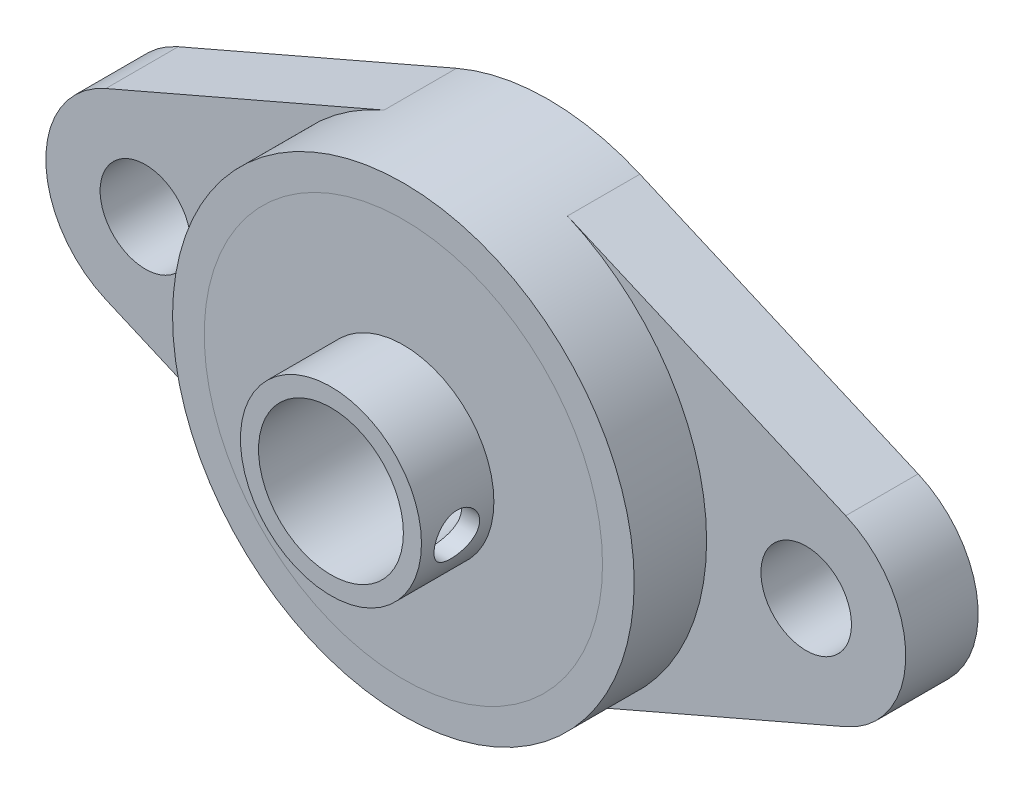
SolidWorks part; units mm, degrees
material "acero"
ref_plane "Alzado" through (0, 0, 0) normal (0, 0, 1) x (1, 0, 0)
ref_plane "Planta" through (0, 0, 0) normal (0, 1, 0) x (1, 0, 0)
ref_plane "Vista lateral" through (0, 0, 0) normal (1, 0, 0) x (0, 0, -1)
sketch "Croquis1" plane through (0, 0, 0) normal (0, 0, 1) x (1, 0, 0)
  line L0 (-18.25, 0) -> (0, 0) construction
  line L1 (0, 0) -> (18.25, 0) construction
  line L2 (-20.4349, -5.0474) -> (-5.0651, -11.7008)
  line L3 (5.0651, -11.7008) -> (20.4349, -5.0474)
  line L4 (5.0651, 11.7008) -> (20.4349, 5.0474)
  line L5 (-20.4349, 5.0474) -> (-5.0651, 11.7008)
  arc A0 (-5.0651, -11.7008) -> (5.0651, -11.7008) centre (0, 0) ccw
  circle A1 centre (0, 0) radius 5
  arc A2 (20.4349, -5.0474) -> (20.4349, 5.0474) centre (18.25, 0) ccw
  circle A3 centre (-18.25, 0) radius 2.5
  circle A4 centre (18.25, 0) radius 2.5
  arc A5 (-20.4349, 5.0474) -> (-20.4349, -5.0474) centre (-18.25, 0) ccw
  arc A7 (5.0651, 11.7008) -> (-5.0651, 11.7008) centre (0, 0) ccw
  dimension "D2" = 5.5
  dimension "D3" = 25.5
  dimension "D4" = 5
  dimension "D5" = 10
  dimension "D1" = 36.5
extrude "Saliente-Extruir1" add sketch "Croquis1" along normal blind 4
sketch "Croquis2" plane through (0, 0, 4) normal (0, 0, 1) x (1, 0, 0)
  circle A0 centre (0, 0) radius 11
  circle A1 centre (0, 0) radius 12.75
  arc A2 (-5.0651, -11.7008) -> (5.0651, -11.7008) centre (0, 0) ccw construction
  dimension "D1" = 22
extrude "Saliente-Extruir2" add sketch "Croquis2" along normal blind 4
sketch "Croquis3" plane through (0, 0, 4) normal (0, 0, 1) x (1, 0, 0)
  circle A0 centre (0, 0) radius 5
  circle A1 centre (0, 0) radius 11
  circle A2 centre (0, 0) radius 11
  dimension "D2" = 10
  dimension "D1" = 0
extrude "Saliente-Extruir3" add sketch "Croquis3" along normal blind 4 separate body
sketch "Croquis5" plane through (0, 0, 0) normal (0, 0, 1) x (1, 0, 0)
  circle A0 centre (0, 0) radius 5
  circle A1 centre (0, 0) radius 4
  dimension "D1" = 8
  dimension "D2" = 10
extrude "Saliente-Extruir4" add sketch "Croquis5" along normal blind 12 separate body
combine bodies "Combinar1" operation type add bodies to combine 106 107
ref_plane "Plane1" through (5, 0, 0) normal (1, 0, 0) x (0, 0, -1)
hole_wizard "M3 Tapped Hole1" positions "Sketch3" profile "Sketch2" tap size "M3" standard "DIN"
sketch "Sketch3" plane through (5, 0, 0) normal (1, 0, 0) x (0, 0, -1)
  line L0 (-12, 5) -> (-12, -5) construction
  point P0 (-10, -0.6713)
  dimension "D1" = 2
sketch "Sketch2" plane through (5, -0.6713, 10) normal (0, 1, 0) x (0, 0, -1)
  line L0 (0, 0) -> (0, 6.2511)
  line L1 (0, 6.2511) -> (1.25, 5.5)
  line L2 (1.25, 5.5) -> (1.25, 0)
  line L5 (1.25, 0) -> (0, 0)
  line L10 (0, 6.2511) -> (-1.25, 5.5) construction
  line L11 (0, -6.35) -> (0, 107.95) construction
  dimension "Tap Drill Dia." = 2.5
  dimension "Tap Drill Depth" = 5.5
  dimension "Drill Angle" = 118
cosmetic thread "Hole Thread1" parameters "D1"=1.4916, "D2"=3
